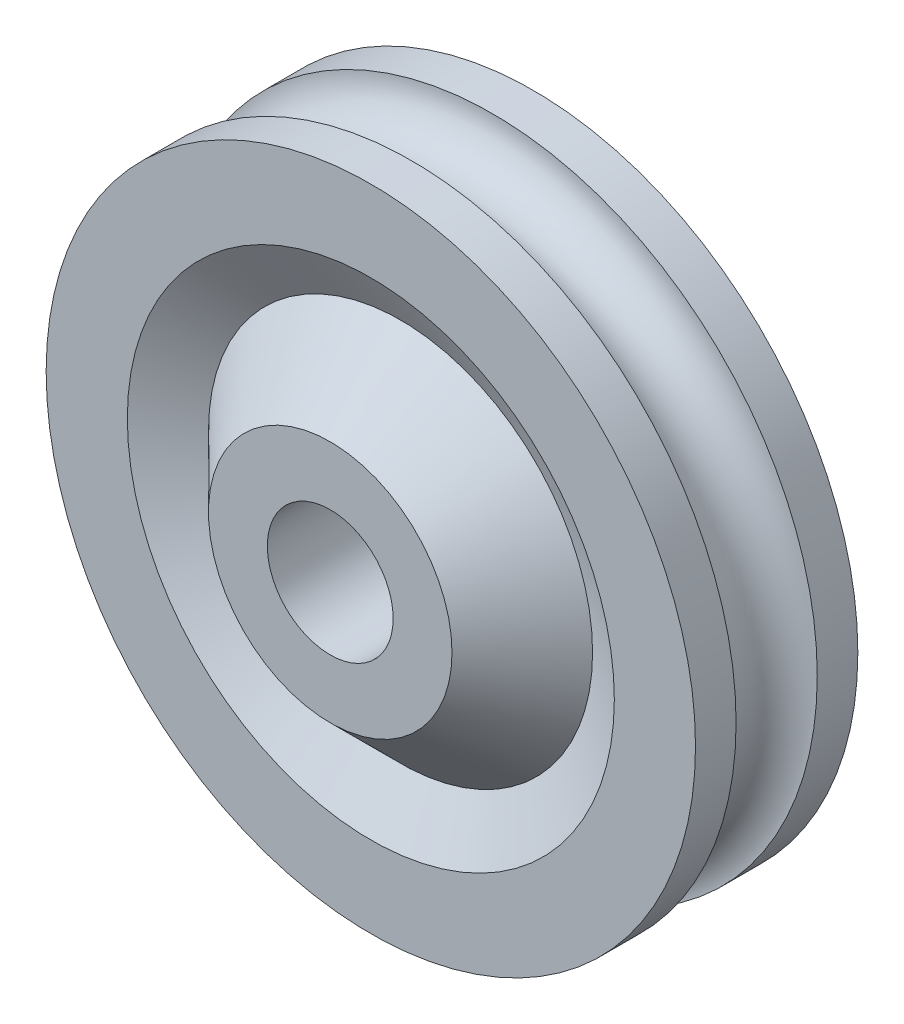
SolidWorks part; units mm, degrees
ref_plane "Front Plane" through (0, 0, 0) normal (0, 0, 1) x (1, 0, 0)
ref_plane "Top Plane" through (0, 0, 0) normal (0, 1, 0) x (1, 0, 0)
ref_plane "Right Plane" through (0, 0, 0) normal (1, 0, 0) x (0, 0, -1)
sketch "Sketch2" plane through (0, 0, 0) normal (0, 1, 0) x (1, 0, 0)
  line L0 (0, 0) -> (64.1086, 0) construction
  line L1 (0, -2) -> (0, -3)
  line L2 (8, -2) -> (0, -2)
  line L3 (8, -2) -> (8, 2)
  line L4 (8, 2) -> (0, 2)
  line L5 (0, -2) -> (0, 2)
  line L6 (8, -2) -> (0, 2) construction
  line L7 (8, 2) -> (0, -2) construction
  line L8 (0, -3) -> (3, -3)
  line L9 (3, -3) -> (3, -1)
  line L10 (3, -1) -> (4.2679, -1)
  line L11 (4.2679, -1) -> (6, -2)
  circle A0 centre (8, 0) radius 1
  point P3 (4, 0)
  dimension "D3" = 2
  dimension "D1" = 4
  dimension "D2" = 8
  dimension "D4" = 3
  dimension "D5" = 1
  dimension "D6" = 2
  dimension "D7" = 30
  dimension "D8" = 5
revolve "Revolve1" add sketch "Sketch2" angle 360 about L5 region at (1.5, 0, 2.5) region at (3.792, 0, -0.1182)
sketch "Sketch3" plane through (0, 0, 3) normal (0, 0, 1) x (1, 0, 0)
  circle A0 centre (0, 0) radius 1.55
  dimension "D1" = 3.1
extrude "Cut-Extrude1" cut sketch "Sketch3" against normal through all
chamfer "Chamfer1" distance 2 angle 45 1 edges at (3, 0, 1)
